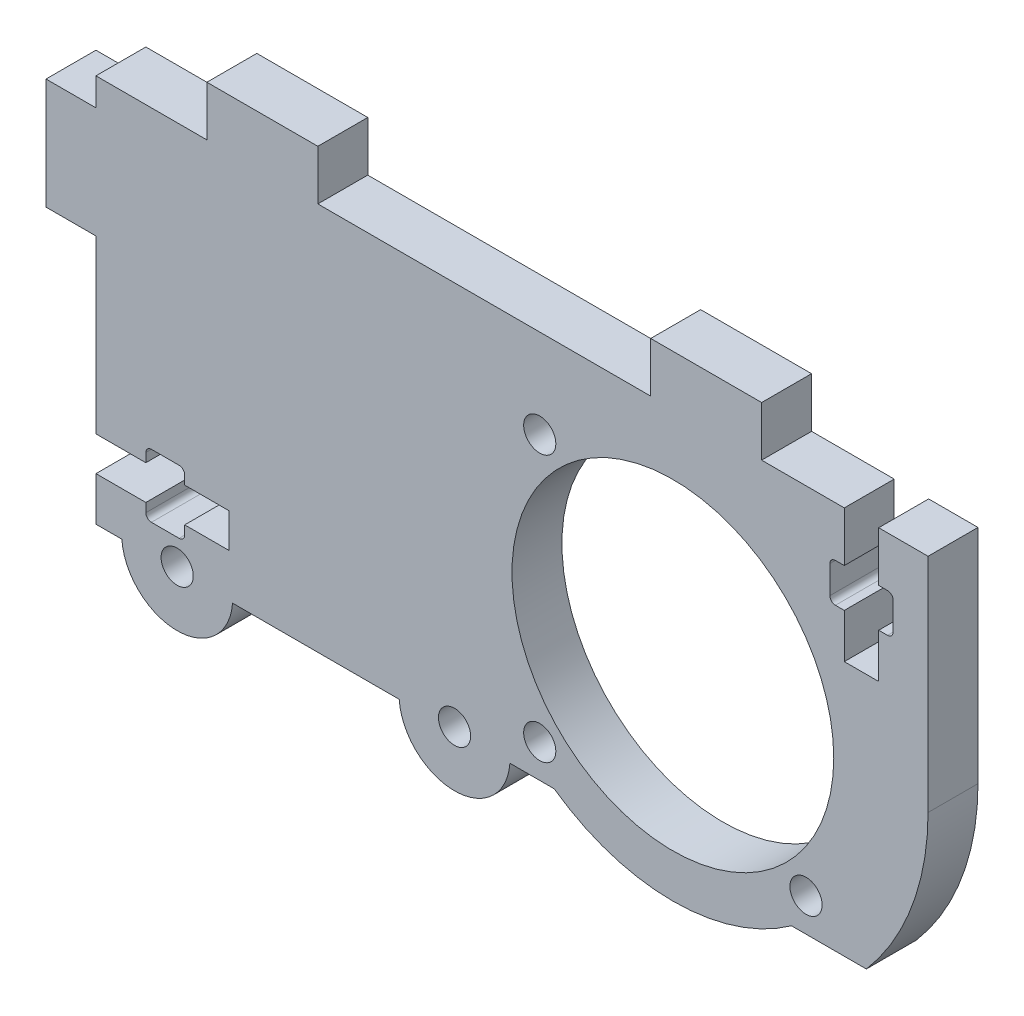
SolidWorks part; units mm, degrees
ref_plane "Front Plane" through (0, 0, 0) normal (0, 0, 1) x (1, 0, 0)
ref_plane "Top Plane" through (0, 0, 0) normal (0, 1, 0) x (1, 0, 0)
ref_plane "Right Plane" through (0, 0, 0) normal (1, 0, 0) x (0, 0, -1)
sketch "Sketch1" plane through (0, 0, 0) normal (0, 0, 1) x (1, 0, 0)
  line L0 (0, 0) -> (0, -35)
  line L1 (0, -35) -> (75, -35)
  line L2 (75, -35) -> (75, 0)
  line L3 (75, 0) -> (0, 0)
  dimension "D1" = 75
  dimension "D2" = 35
extrude "MainShape" add sketch "Sketch1" along normal blind 4.5
sketch "Sketch2" plane through (0, 0, 4.5) normal (0, 0, 1) x (1, 0, 0)
  line L0 (0, -2.5) -> (-4.5, -2.5)
  line L1 (0, 0) -> (0, -35) construction
  line L2 (-4.5, -2.5) -> (-4.5, -12.5)
  line L3 (-4.5, -12.5) -> (0, -12.5)
  line L4 (0, -12.5) -> (0, -2.5)
  line L5 (-4.5, -7.5) -> (0, -7.5) construction
  dimension "D1" = 10
  dimension "D2" = 4.5
  dimension "D3" = 7.5
extrude "RearTab" add sketch "Sketch2" against normal through all
sketch "Sketch3" plane through (0, 0, 4.5) normal (0, 0, 1) x (1, 0, 0)
  line L0 (75, 0) -> (0, 0) construction
  line L1 (10, 0) -> (20, 0)
  line L2 (10, 0) -> (10, 4.5)
  line L3 (10, 4.5) -> (20, 4.5)
  line L4 (20, 0) -> (20, 4.5)
  line L5 (15, 4.5) -> (15, 0) construction
  line L6 (50, 0) -> (60, 0)
  line L7 (50, 0) -> (50, 4.5)
  line L8 (50, 4.5) -> (60, 4.5)
  line L9 (60, 0) -> (60, 4.5)
  line L10 (55, 4.5) -> (55, 0) construction
  dimension "D1" = 4.5
  dimension "D2" = 10
  dimension "D3" = 40
  dimension "D4" = 15
extrude "Boss-Extrude3" add sketch "Sketch3" against normal through all
sketch "Sketch4" plane through (0, 0, 4.5) normal (0, 0, 1) x (1, 0, 0)
  line L0 (69, 0) -> (69, -12) construction
  line L1 (75, 0) -> (60, 0) construction
  line L2 (70.55, -12) -> (67.45, -12) construction
  line L3 (67.45, -12) -> (67.45, 0) construction
  line L4 (67.45, 0) -> (67.45, -4.5)
  line L5 (67.45, -4.5) -> (66.65, -4.5)
  line L6 (66.15, -5) -> (66.15, -7.5)
  line L7 (66.65, -8) -> (67.45, -8)
  line L8 (67.45, -8) -> (67.45, -12)
  line L9 (67.45, -12) -> (70.55, -12)
  line L10 (67.45, 0) -> (70.55, 0)
  line L11 (70.55, -12) -> (70.55, 0) construction
  line L12 (70.55, -8) -> (70.55, -12)
  line L13 (71.35, -8) -> (70.55, -8)
  line L14 (71.85, -5) -> (71.85, -7.5)
  line L15 (70.55, -4.5) -> (71.35, -4.5)
  line L16 (70.55, 0) -> (70.55, -4.5)
  arc A0 (66.15, -7.5) -> (66.65, -8) centre (66.65, -7.5) ccw
  arc A1 (66.65, -4.5) -> (66.15, -5) centre (66.65, -5) ccw
  arc A2 (71.35, -4.5) -> (71.85, -5) centre (71.35, -5) cw
  arc A3 (71.85, -7.5) -> (71.35, -8) centre (71.35, -7.5) cw
  point P13 (66.15, -8)
  point P16 (66.15, -4.5)
  point P27 (71.85, -4.5)
  point P28 (71.85, -8)
  dimension "D7" = 0.5
  dimension "D1" = 12
  dimension "D2" = 1.55
  dimension "D3" = 3.5
  dimension "D4" = 2.85
  dimension "D5" = 8
  dimension "D6" = 69
extrude "Cut-Extrude1" cut sketch "Sketch4" against normal through all
sketch "Sketch5" plane through (0, 0, 4.5) normal (0, 0, 1) x (1, 0, 0)
  line L0 (45.0208, 0) -> (45.0208, 4.5) construction
  line L1 (42.5416, 0) -> (47.5, 0)
  line L2 (42.5416, 0) -> (42.5416, -5.18)
  line L3 (42.5416, -5.18) -> (47.5, -5.18)
  line L4 (47.5, 0) -> (47.5, -5.18)
  line L5 (42.5416, 0) -> (47.5, -5.18) construction
  line L6 (42.5416, -5.18) -> (47.5, 0) construction
  line L7 (42, -4.18) -> (48, -4.18) construction
  line L8 (50, 0) -> (20, 0) construction
  line L9 (48, -4.18) -> (48, -1.18) construction
  line L10 (48, -2.68) -> (58, -2.68) construction
  line L11 (48, -4.18) -> (48, -1.18) construction
  line L12 (58, -1.18) -> (58, -4.18) construction
  line L13 (53, -2.68) -> (53, 0) construction
  line L14 (0, 0) -> (19.5, 0) construction
  line L15 (63.4584, -5.18) -> (58.5, 0) construction
  line L16 (63.4584, 0) -> (58.5, -5.18) construction
  line L17 (58.5, 0) -> (58.5, -5.18)
  line L18 (63.4584, -5.18) -> (58.5, -5.18)
  line L19 (63.4584, 0) -> (63.4584, -5.18)
  line L20 (63.4584, 0) -> (58.5, 0)
  line L21 (42.5416, -5.18) -> (47.5, 0) construction
  point P0 (45.0208, -2.59)
  point P27 (60.9792, -2.59)
  dimension "D1" = 1
  dimension "D2" = 0
  dimension "D3" = 0.5
extrude "Cut-Extrude2" [suppressed] cut sketch "Sketch5" against normal through all
sketch "Sketch6" plane through (0, 0, 4.5) normal (0, 0, 1) x (1, 0, 0)
  line L0 (52, -20) -> (40, -8) construction
  line L2 (52, -34.5) -> (52, -5.5) construction
  line L3 (52, -20) -> (37.5, -20) construction
  line L4 (52, -20) -> (64, -8) construction
  line L5 (52, -20) -> (64, -32) construction
  line L6 (52, -20) -> (40, -32) construction
  circle A0 centre (52, -20) radius 14.5
  circle A1 centre (40, -8) radius 1.45
  circle A3 centre (64, -32) radius 1.45
  circle A4 centre (40, -32) radius 1.45
  dimension "D1" = 29
  dimension "D4" = 2.9
  dimension "D2" = 52
  dimension "D3" = 20
  dimension "D5" = 12
  dimension "D6" = 45
extrude "Cut-Extrude3" cut sketch "Sketch6" against normal through all
sketch "Sketch7" plane through (0, 0, 4.5) normal (0, 0, 1) x (1, 0, 0)
  line L0 (0, -35) -> (62.6919, -35)
  arc A0 (41.3081, -35) -> (62.6919, -35) centre (52, -20) ccw
  circle A1 centre (52, -20) radius 14.5 construction
  circle A2 centre (64, -32) radius 1.45 construction
extrude "Boss-Extrude4" add sketch "Sketch7" against normal through all contours L0 A0 region at (52, -36.3797, 4.5)
sketch "Sketch8" [suppressed] plane through (0, 0, 4.5) normal (0, 0, 1) x (1, 0, 0)
  line L1 (0, -35) -> (39.1367, -35) construction
  line L18 (15, -35) -> (15, -9.316) construction
  line L19 (6.3379, -28.8128) -> (15, -37.4749) construction
  line L20 (8.8128, -26.3379) -> (17.4749, -35) construction
  line L21 (6.3379, -28.8128) -> (8.8128, -26.3379) construction
  line L22 (15, -35) -> (7.5754, -27.5754) construction
  line L23 (15, -37.4749) -> (11.0756, -33.5504)
  line L24 (11.0756, -33.5504) -> (10.1917, -34.4343)
  line L25 (10.1917, -34.4343) -> (7.2218, -31.4645)
  line L26 (7.2218, -31.4645) -> (8.1057, -30.5806)
  line L27 (8.1057, -30.5806) -> (6.3379, -28.8128)
  line L28 (15, -37.4749) -> (15, -35)
  line L29 (17.4749, -35) -> (15, -35)
  line L30 (8.8128, -26.3379) -> (6.3379, -28.8128)
  line L31 (10.5806, -28.1057) -> (8.8128, -26.3379)
  line L32 (11.4645, -27.2218) -> (10.5806, -28.1057)
  line L33 (14.4343, -30.1917) -> (11.4645, -27.2218)
  line L34 (13.5504, -31.0756) -> (14.4343, -30.1917)
  line L35 (17.4749, -35) -> (13.5504, -31.0756)
  dimension "D7" = 15
extrude "Cut-Extrude4" [suppressed] cut sketch "Sketch8" against normal through all
sketch "Sketch10" [suppressed] plane through (0, 0, 4.5) normal (0, 0, 1) x (1, 0, 0)
  line L0 (17.4749, -35) -> (21.7175, -30.7574)
  line L1 (21.7175, -30.7574) -> (25.253, -34.2929)
  line L2 (25.253, -34.2929) -> (24.5459, -35)
  line L3 (17.4749, -35) -> (39.1367, -35) construction
  line L4 (24.5459, -35) -> (17.4749, -35)
  line L5 (17.4749, -35) -> (13.5504, -31.0756) construction
  dimension "D1" = 5
  dimension "D2" = 6
extrude "Cut-Extrude6" [suppressed] cut sketch "Sketch10" against normal through all
sketch "Sketch12" plane through (0, 0, 4.5) normal (0, 0, 1) x (1, 0, 0)
  line L0 (7.3224, -34.6526) -> (32.3224, -34.6526) construction
  circle A0 centre (32.3224, -34.6526) radius 5
  circle A1 centre (7.3224, -34.6526) radius 5
  dimension "D1" = 10
  dimension "D2" = 10
  dimension "D3" = 25
  dimension "D4" = 34.6526
  dimension "D5" = 7.3224
extrude "Boss-Extrude5" add sketch "Sketch12" against normal through all
sketch "Sketch11" plane through (0, 0, 4.5) normal (0, 0, 1) x (1, 0, 0)
  line L0 (0, -29.5) -> (12, -29.5) construction
  line L1 (0, -12.5) -> (0, -35) construction
  line L2 (12, -31.05) -> (12, -27.95) construction
  line L3 (12, -27.95) -> (0, -27.95) construction
  line L4 (0, -31.05) -> (0, -27.95)
  line L5 (0, -27.95) -> (4.5, -27.95)
  line L6 (4.5, -27.95) -> (4.5, -27.15)
  line L7 (5, -26.65) -> (7.5, -26.65)
  line L8 (8, -27.15) -> (8, -27.95)
  line L9 (8, -27.95) -> (12, -27.95)
  line L10 (12, -27.95) -> (12, -31.05)
  line L11 (12, -31.05) -> (0, -31.05) construction
  line L12 (8, -31.05) -> (12, -31.05)
  line L13 (8, -31.85) -> (8, -31.05)
  line L14 (5, -32.35) -> (7.5, -32.35)
  line L15 (4.5, -31.05) -> (4.5, -31.85)
  line L16 (0, -31.05) -> (4.5, -31.05)
  line L17 (-4.5, -2.5) -> (-4.5, -12.5) construction
  arc A0 (7.5, -26.65) -> (8, -27.15) centre (7.5, -27.15) cw
  arc A1 (4.5, -27.15) -> (5, -26.65) centre (5, -27.15) cw
  arc A2 (4.5, -31.85) -> (5, -32.35) centre (5, -31.85) ccw
  arc A3 (7.5, -32.35) -> (8, -31.85) centre (7.5, -31.85) ccw
  point P12 (8, -26.65)
  point P15 (4.5, -26.65)
  point P26 (4.5, -32.35)
  point P27 (8, -32.35)
  point P28 (-4.5, -7.5)
  dimension "D1" = 12
  dimension "D2" = 1.55
  dimension "D3" = 3.5
  dimension "D4" = 2.85
  dimension "D5" = 8
  dimension "D6" = 0.5
  dimension "D7" = 22
extrude "Cut-Extrude7" cut sketch "Sketch11" against normal through all
sketch "Sketch13" plane through (0, 0, 4.5) normal (0, 0, 1) x (1, 0, 0)
  circle A0 centre (7.3224, -34.6526) radius 1.45
  circle A1 centre (32.3224, -34.6526) radius 1.45
  arc A2 (2.3345, -35) -> (12.3103, -35) centre (7.3224, -34.6526) ccw construction
  arc A3 (27.3345, -35) -> (37.3103, -35) centre (32.3224, -34.6526) ccw construction
  dimension "D1" = 2.9
extrude "Cut-Extrude8" cut sketch "Sketch13" against normal through all
sketch "Sketch14" plane through (0, 0, 4.5) normal (0, 0, 1) x (1, 0, 0)
  line L0 (75, -35) -> (75, 0) construction
  line L1 (69.4356, -35) -> (75, -35)
  line L2 (75, -35) -> (75, -20)
  arc A0 (69.4356, -35) -> (75, -20) centre (52, -20) ccw
  circle A1 centre (52, -20) radius 14.5 construction
extrude "SmoothEdge" cut sketch "Sketch14" against normal through all
equation "\"X-ROD-SPACING\"=45"
equation "\"Y-ROD-SPACING\"=75"
equation "\"Z-ROD-SPACING\"=17.5"
equation "\"Y-BED-OFFSET\"=2"
equation "\"Y-BED-ROD-INSET\"=3.5"
equation "\"Y-BED-SCREW-SPACING\"=209"
equation "\"Y-BED-SCREW-CUTOUT-SLOT-HEIGHT\"=2"
equation "\"T-SLOT-NUT-FILLET-RADIUS\"=0.5"
equation "\"T-SLOT-SCREW-SHAFT-RADIUS\"=1.55"
equation "\"T-SLOT-SCREW-SHAFT-CUTOUT-LENGTH\"=11"
equation "\"T-SLOT-NUT-DEPTH\"=3.5"
equation "\"T-SLOT-NUT-WIDTH\"=2.85"
equation "\"T-SLOT-NUT-END-DISTANCE\"=8"
equation "\"ACRYLIC-THICKNESS\"=10"
equation "\"ACRYLIC-THICKNESS2\"=4.5"
equation "\"ACRYLIC-TAB-CUTOUT-SIZE\"=\"ACRYLIC-THICKNESS\"+\"ACRYLIC-TAB-TOLERANCE\"*2"
equation "\"ACRYLIC-TAB-TOLERANCE\"=-.05"
equation "\"ACRYLIC-TAB-WIDTH\"=\"ACRYLIC-THICKNESS\""
equation "\"ACRYLIC-M3-HOLE\"=2.9"
equation "\"SMOOTHROD-CAP-SCREW-DISTANCE\"=20"
equation "\"FRAME-WIDTH-INNER\"=370"
equation "\"NEMA17-HOLE-SPACING\"=31"
equation "\"NEMA17-CENTRAL-CUTOUT\"=22.5"
equation "\"Z-BRACKET-REACH\"=55"
equation "\"Z-ROD-INSET\"=13.5"
equation "\"TOP-BRACKET-SPACING\"=40"
equation "\"SMOOTHROD-X-LENGTH\"=350"
equation "\"SMOOTHROD-Y-LENGTH\"=350"
equation "\"SMOOTHROD-Z-LENGTH\"=350"
equation "\"SMOOTHROD-TIGHTENING-HEADROOM\"=.25"
equation "\"LEADSCREW-Z-LENGTH\"=300"
equation "\"SCREW-LENGTH-FRAME\"=\"ACRYLIC-THICKNESS\" + 10"
equation "\"SCREW-LENGTH-MOTOR\"=\"ACRYLIC-THICKNESS\" + 5"
equation "\"SCREW-LENGTH-EXTRUDER\"=28"
equation "\"SCREW-HEAD-RADIUS\"=6"
equation "\"PRINTED-M3-HOLE\"=3.5"
equation "\"PRINTED-X-SMOOTHROD-DIAMETER\"=9.0"
equation "\"PRINTED-X-SMOOTHROD-CUTOUT\"=10"
equation "\"PRINTED-X-BASE-HEIGHT\"=10"
equation "\"PRINTED-LM8UU-CUTOUT-SIZE\"=15.5"
equation "\"PRINTED-LM8UU-CUTOUT-LENGTH\"=24.5"
equation "\"PRINTED-X-IDLER-HEIGHT\"=16"
equation "\"PRINTED-M3-NUT-AF\"=6.25"
equation "\"PSU-MOUNTING-WIDTH\"=95"
equation "\"PSU-MOUNTING-HEIGHT\"=177"
equation "\"Y-BELT-TO-ROD-DISTANCE\"=20"
equation "\"SPOOL-HOLDER-ROD-SPACING\"=150"
equation "\"ACRYLIC-X-CARRIAGE-WIDTH\"=55"
equation "\"ACRYLIC-X-CARRIAGE-HEIGHT\"=75"
equation "\"ACRYLIC-X-CARRIAGE-LM8UU-CUTOUT-WIDTH\"=24.25"
equation "\"ACRYLIC-X-CARRIAGE-LM8UU-CUTOUT-HEIGHT\"=11.0"
equation "\"ACRYLIC-X-CARRIAGE-SCREW-SPACING-X\"=15"
equation "\"ACRYLIC-X-CARRIAGE-SCREW-SPACING-Y\"=33"
equation "\"ACRYLIC-X-CARRIAGE-CENTER-TAB-SPACING\"=14"
equation "\"ACRYLIC-X-CARRIAGE-EXTRUDER-OFFSET\"=26"
equation "\"ACRYLIC-X-CARRIAGE-EXTRUDER-ANGLE\"=90"
equation "\"ACRYLIC-X-CARRIAGE-EXTRUDER-SHELF-DEPTH\"=\"ACRYLIC-X-CARRIAGE-EXTRUDER-OFFSET\" + 28"
equation "\"ACRYLIC-X-CARRIAGE-EXTRUDER-BRACE-SPACING\"=23"
equation "\"ACRYLIC-X-CARRIAGE-EXTRUDER-BRACE-TAB-OFFSET\"=20"
equation "\"ACRYLIC-X-CARRIAGE-EXTRUDER-BRACE-HEIGHT\"=35"
equation "\"ACRYLIC-X-CARRIAGE-EXTRUDER-BRACE-SCREW-SPACING\"=22"
equation "\"ACRYLIC-X-CARRIAGE-DUAL-WIDTH-MULTIPLIER\"=1.65"
equation "\"ACRYLIC-X-CARRIAGE-DUAL-HOTEND-SPACING\"=42"
equation "\"ACRYLIC-X-CARRIAGE-DUAL-WIDTH\"=75"
equation "\"ACRYLIC-X-CARRIAGE-DUAL-FAN-OFFSET\"=52"
equation "\"ACRYLIC-X-CARRIAGE-DUAL-FAN-HEIGHT\"=20"
equation "\"ACRYLIC-X-CARRIAGE-DUAL-HOTEND-SEPARATION\"=36"
equation "\"ACRYLIC-X-CARRIAGE-DUAL-MOUNT-PLATE-DEPTH\"=75"
equation "\"ACRYLIC-X-CARRIAGE-DUAL-MOUNT-BRACE-WIDTH\"=33"
equation "\"ACRYLIC-X-CARRIAGE-DUAL-MOUNT-SCREW-WIDTH\"=40"
equation "\"BLOWER-FAN-WIDTH\"=15"
equation "\"D1@Sketch1\"=\"ACRYLIC-X-CARRIAGE-DUAL-MOUNT-PLATE-DEPTH\""
equation "\"D2@Sketch1\"=\"ACRYLIC-X-CARRIAGE-EXTRUDER-BRACE-HEIGHT\""
equation "\"D1@MainShape\" = \"ACRYLIC-THICKNESS2\""
equation "\"D1@Sketch2\"=\"ACRYLIC-TAB-WIDTH\""
equation "\"D2@Sketch2\"=\"ACRYLIC-THICKNESS2\""
equation "\"D1@Sketch3\"=\"ACRYLIC-THICKNESS2\""
equation "\"D2@Sketch3\"=\"ACRYLIC-TAB-WIDTH\""
equation "\"D1@Sketch4\"=\"T-SLOT-SCREW-SHAFT-CUTOUT-LENGTH\"+1"
equation "\"D2@Sketch4\"=\"T-SLOT-SCREW-SHAFT-RADIUS\""
equation "\"D3@Sketch4\"=\"T-SLOT-NUT-DEPTH\""
equation "\"D4@Sketch4\"=\"T-SLOT-NUT-WIDTH\""
equation "\"D5@Sketch4\"=\"T-SLOT-NUT-END-DISTANCE\""
equation "\"D7@Sketch4\"=\"T-SLOT-NUT-FILLET-RADIUS\""
equation "\"D2@Sketch6\"=\"ACRYLIC-X-CARRIAGE-DUAL-FAN-OFFSET\""
equation "\"D3@Sketch6\"=\"ACRYLIC-X-CARRIAGE-DUAL-FAN-HEIGHT\""
equation "\"D4@Sketch6\"=\"ACRYLIC-M3-HOLE\""
equation "\"D1@Sketch11\"=\"T-SLOT-SCREW-SHAFT-CUTOUT-LENGTH\"+1"
equation "\"D2@Sketch11\"=\"T-SLOT-SCREW-SHAFT-RADIUS\""
equation "\"D3@Sketch11\"=\"T-SLOT-NUT-DEPTH\""
equation "\"D4@Sketch11\"=\"T-SLOT-NUT-WIDTH\""
equation "\"D5@Sketch11\"=\"T-SLOT-NUT-END-DISTANCE\""
equation "\"D6@Sketch11\"=\"T-SLOT-NUT-FILLET-RADIUS\""
equation "\"D1@Sketch13\"=\"ACRYLIC-M3-HOLE\""
